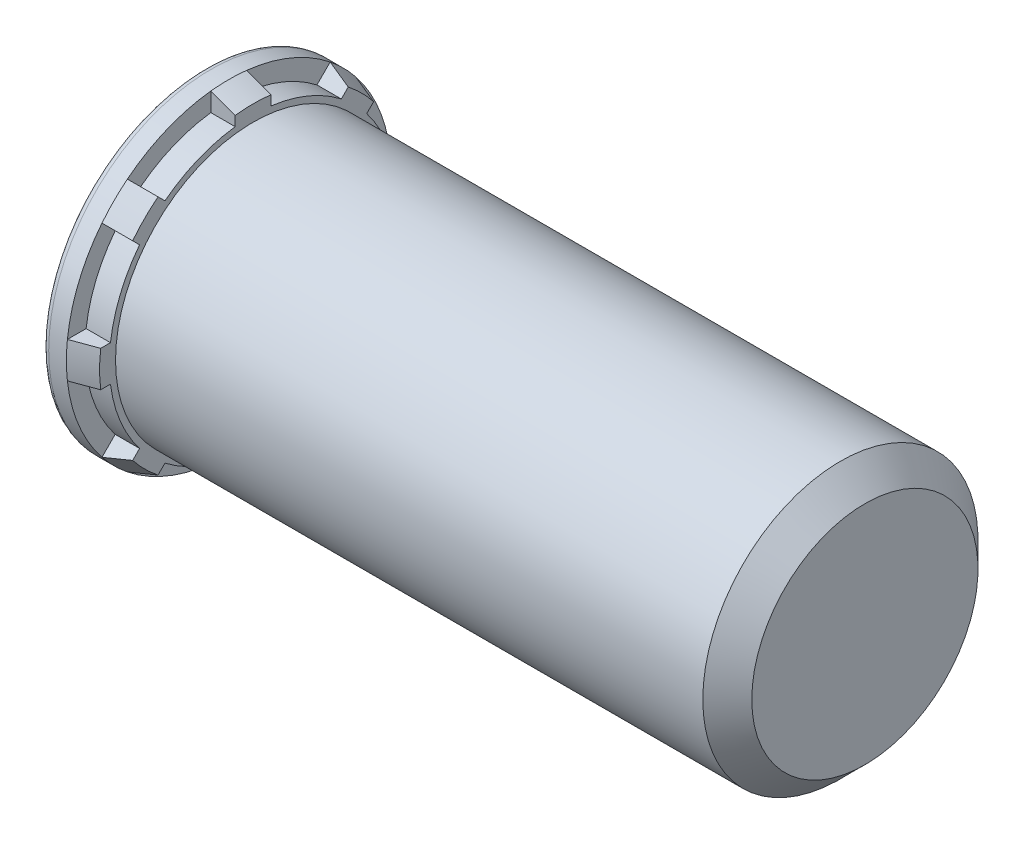
SolidWorks part; units mm, degrees
revolve "BaseBody" add sketch "BodySke" angle 360 about L6 other way angle 7.5
sketch "BodySke" plane through (0, 0, 0) normal (0, 0, 1) x (1, 0, 0)
  line L0 (-0.4425, 2.8295) -> (-0.4425, 0)
  line L1 (0.4425, 2.7889) -> (0.4425, 2.5)
  line L2 (0, 2.95) -> (0.4425, 2.7889)
  line L3 (0.4425, 2.5) -> (11.1125, 2.5)
  line L4 (11.5575, 2.055) -> (11.5575, 0)
  line L5 (11.5575, 0) -> (-0.4425, 0)
  line L6 (0, 0) -> (50.554, 0) construction
  line L7 (-0.4425, 2.8295) -> (-0.44, 2.8295)
  line L8 (11.5575, 2.055) -> (11.1125, 2.5)
  line L9 (-0.322, 2.95) -> (0, 2.95)
  line L11 (0.8, 19.05) -> (0.8, -3.175) construction
  line L13 (-0.44, 2.8295) -> (-0.44, 2.832)
  arc A0 (-0.44, 2.832) -> (-0.322, 2.95) centre (-0.322, 2.832) cw
  dimension "Fillet_rad" = 0.118
  dimension "Minor_dia" = 4.11
  dimension "Diameter" = 5
  dimension "H_dia" = 5.9
  dimension "Advance" = 0.8
  dimension "D1" = 20
  dimension "Length" = 12
  dimension "D2" = 0.0025
  dimension "D3" = 0.0025
  dimension "Clinch_ht" = 0.4425
  dimension "Head_ht" = 0.885
cosmetic thread "ThreadCosmetic" [suppressed] parameters "Thread_length"=9.3, "Thread_minor"=4.11
ref_plane "Plane1" through (0, 0, 0) normal (0, 0, 1) x (1, 0, 0)
ref_plane "Plane2" through (0, 0, 0) normal (0, 1, 0) x (1, 0, 0)
ref_plane "Plane3" through (0, 0, 0) normal (1, 0, 0) x (0, 0, -1)
sketch "ThdSchSke" plane through (0, 0, 0) normal (0, 0, 1) x (1, 0, 0)
  line L0 (2.2575, -2.055) -> (1.9459, -2.5)
  line L1 (2.2575, -2.055) -> (2.5691, -2.5)
  line L2 (2.5691, -2.5) -> (2.5691, -3.125)
  line L3 (-3.175, 0) -> (5.1513, 0) construction
  line L5 (2.5691, -3.125) -> (1.9459, -3.125)
  line L6 (1.9459, -3.125) -> (1.9459, -2.5)
  line L7 (-0.4425, 2.8295) -> (-0.4425, -2.8295) construction
  dimension "Diameter" = 5
  dimension "Thread_minor" = 4.11
  dimension "Start" = 2.7
revolve "ThreadSchematic" [suppressed] cut sketch "ThdSchSke" angle 360 about L3
pattern_linear "ThdSchPat" [suppressed]
sketch "RibCutSke" plane through (0.4425, 1.7944, -0.091) normal (1, 0, 0) x (0, 0, -1)
  line L0 (0.2354, 0.7976) -> (0.2354, 1.1375)
  line L1 (1.5112, 0.2692) -> (1.7515, 0.5095)
  line L2 (0.2354, 0.6842) -> (0.2354, 0.0891) construction
  line L3 (-0.091, -1.7944) -> (-0.091, 5.0239) construction
  line L4 (-0.091, -1.7944) -> (0.2354, 0.6842) construction
  line L5 (-0.091, -1.7944) -> (1.431, 0.189) construction
  line L6 (1.431, 0.189) -> (1.0152, -0.2268) construction
  arc A1 (1.5112, 0.2692) -> (0.2354, 0.7976) centre (-0.091, -1.7944) ccw
  arc A2 (1.7515, 0.5095) -> (0.2354, 1.1375) centre (-0.091, -1.7944) ccw
  circle A3 centre (-0.091, -1.7944) radius 2.7889 construction
  circle A4 centre (-0.091, -1.7944) radius 2.5 construction
  dimension "Rib_root_half_angle" = 7.5
  dimension "Rib_root_gap_angle" = 30
  dimension "Angle" = 45
extrude "RibCut" cut sketch "RibCutSke" against normal blind 0.4425
pattern_circular "RibCutsPat" count 8 every 45 about axis through (0, 0, 0) along (1, 0, 0) of "RibCut"
equation "' \"Length@BodySke\" = 12"
equation "' \"H_dia@BodySke\" = 5.9"
equation "' \"Start@ThdSchSke\" = 2.7"
equation "' \"Diameter@BodySke\" = 5"
equation "' \"Minor_dia@BodySke\" = 4.11"
equation "' \"Advance@BodySke\" = 0.8"
equation "\"Fillet_rad@BodySke\" =   \"H_dia@BodySke\" *0.02"
equation "\"Clinch_ht@BodySke\" = \"H_dia@BodySke\" * 0.075"
equation "\"Head_ht@BodySke\" =  \"H_dia@BodySke\" * 0.15"
equation "\"Num_ribs@RibCutsPat\" = 8"
equation "\"Angle@RibCutSke\" =\"Angle@RibCutsPat\""
equation "\"Rib_root_half_angle@RibCutSke\" = \"Angle@RibCutSke\" / 6"
equation "\"Rib_root_gap_angle@RibCutSke\" = \"Angle@RibCutSke\" - (2 * \"Rib_root_half_angle@RibCutSke\" )"
equation "\"Rib_root_dia@RibCutSke\" = \"Diameter@BodySke\""
equation "\"Inner_dia@RibCutSke\" = \"Diameter@BodySke\" + ( \"H_dia@BodySke\" - \"Diameter@BodySke\" ) / 4"
equation "\"Outer_dia@RibCutSke\" = \"H_dia@BodySke\""
equation "\"Depth@RibCut\" = \"Clinch_ht@BodySke\""
equation "\"Thread_length@ThreadCosmetic\" = \"Length@BodySke\" - \"Start@ThdSchSke\""
equation "\"Thread_minor@ThreadCosmetic\" = \"Minor_dia@BodySke\""
equation "\"Thread_minor@ThdSchSke\" = \"Minor_dia@BodySke\""
equation "\"Diameter@ThdSchSke\" = \"Diameter@BodySke\""
equation "\"Overcut@ThdSchSke\" = \"Diameter@BodySke\" * 1.25"
equation "\"Num_threads@ThdSchPat\" = int( \"Thread_length@ThreadCosmetic\" / \"Advance@BodySke\" + 0.999 )  + 1"
equation "\"Advance@ThdSchPat\" = \"Thread_length@ThreadCosmetic\" /  (\"Num_threads@ThdSchPat\" - 1) 'relax it"
equation "\"Num_threads@ThdSchPat\" = \"Num_threads@ThdSchPat\" - sgn( \"Num_threads@ThdSchPat\" - 1) '---chamfered tips only---"
